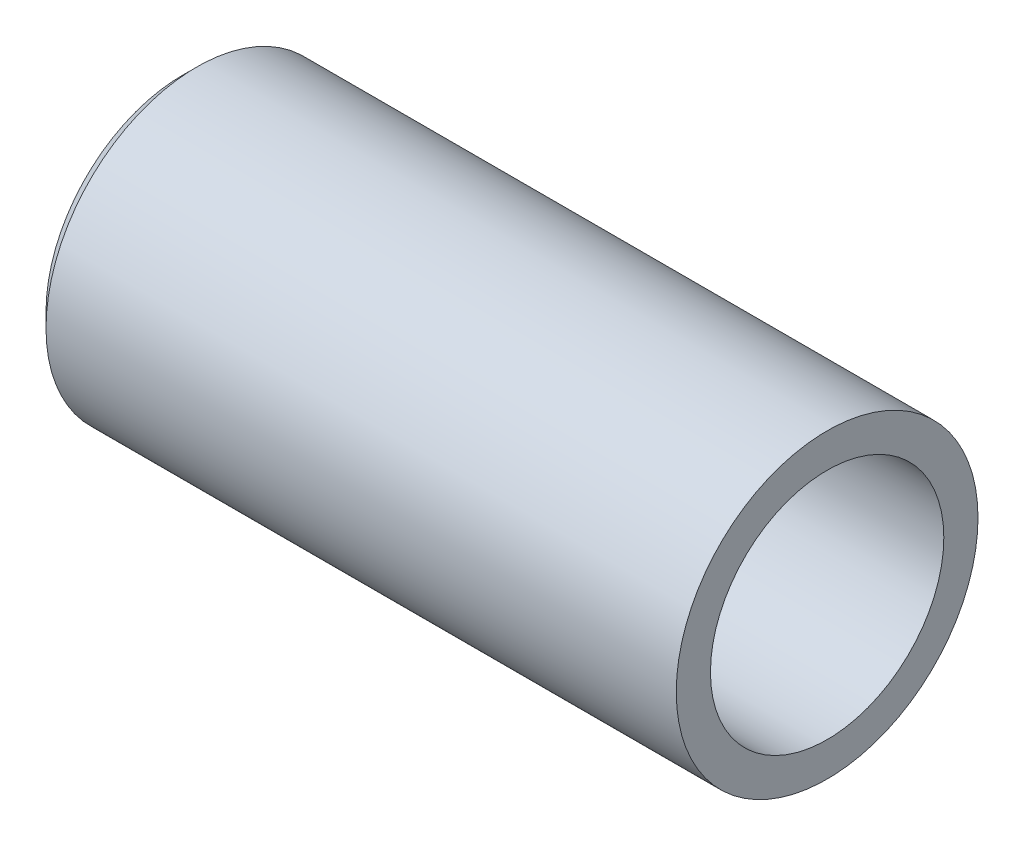
SolidWorks part; units mm, degrees
material "6061-T6 (SS)"
ref_plane "Front Plane" through (0, 0, 0) normal (0, 0, 1) x (1, 0, 0)
ref_plane "Top Plane" through (0, 0, 0) normal (0, 1, 0) x (1, 0, 0)
ref_plane "Right Plane" through (0, 0, 0) normal (1, 0, 0) x (0, 0, -1)
sketch "Sketch1" plane through (0, 0, 0) normal (0, 0, 1) x (1, 0, 0)
  line L0 (0, 0) -> (22.1407, 0) construction
  line L1 (0.9939, 5.2957) -> (23.1179, 5.2957)
  line L3 (0.4969, 4.0957) -> (23.1179, 4.0958)
  line L4 (23.3719, 5.2957) -> (23.3719, 1.3364) construction
  line L5 (23.1179, 5.2957) -> (23.1179, 4.0958)
  line L8 (0.4969, 4.0957) -> (0.4969, 4.7987)
  line L9 (0.4969, 4.7987) -> (0.9939, 5.2957)
  line L15 (0.4969, -7.9375) -> (0.4969, 7.9375) construction
  line L16 (23.3719, 12.0262) -> (23.3719, 15.8235) construction
  dimension "D4" = 45
  dimension "D2" = 1.2
  dimension "D3" = 0.254
  dimension "D1" = 8.1915
revolve "Revolve1" add sketch "Sketch1" angle 360 about L0
equation "\"D2@Sketch1\"=1.2mm"
equation "\"D1@Sketch1\"=5/16 + 0.01"
